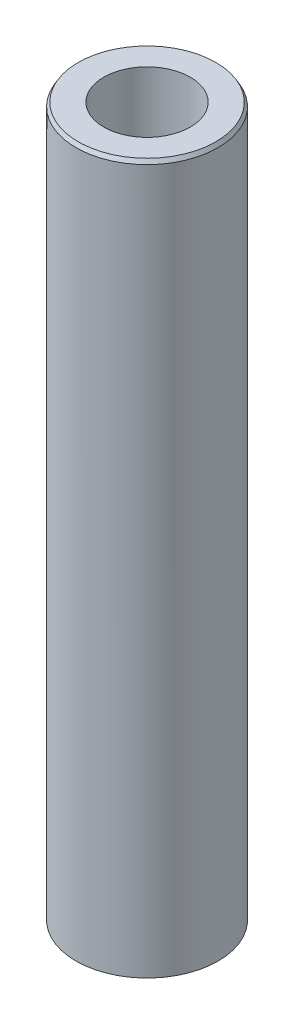
SolidWorks part; units mm, degrees
ref_plane "Front Plane" through (0, 0, 0) normal (0, 0, 1) x (1, 0, 0)
ref_plane "Top Plane" through (0, 0, 0) normal (0, 1, 0) x (1, 0, 0)
ref_plane "Right Plane" through (0, 0, 0) normal (1, 0, 0) x (0, 0, -1)
sketch "Sketch1" plane through (0, 0, 0) normal (0, 1, 0) x (1, 0, 0)
  circle A0 centre (0, 0) radius 60
  dimension "SHAFT_OD" = 120
extrude "Boss-Extrude1" add sketch "Sketch1" along normal blind 600
sketch "Sketch2" plane through (0, 0, 0) normal (0, 1, 0) x (1, 0, 0)
  circle A0 centre (0, 0) radius 36.5134
  dimension "BORE_D" = 73.0267
extrude "Cut-Extrude1" cut sketch "Sketch2" along normal through all
chamfer "Chamfer1" distance 3.3176 angle 30 2 edges at (0, 600, 60) (0, 0, 60) first distance on face at (0, 600, 60) first distance on face at (0, 0, 36.5134)
